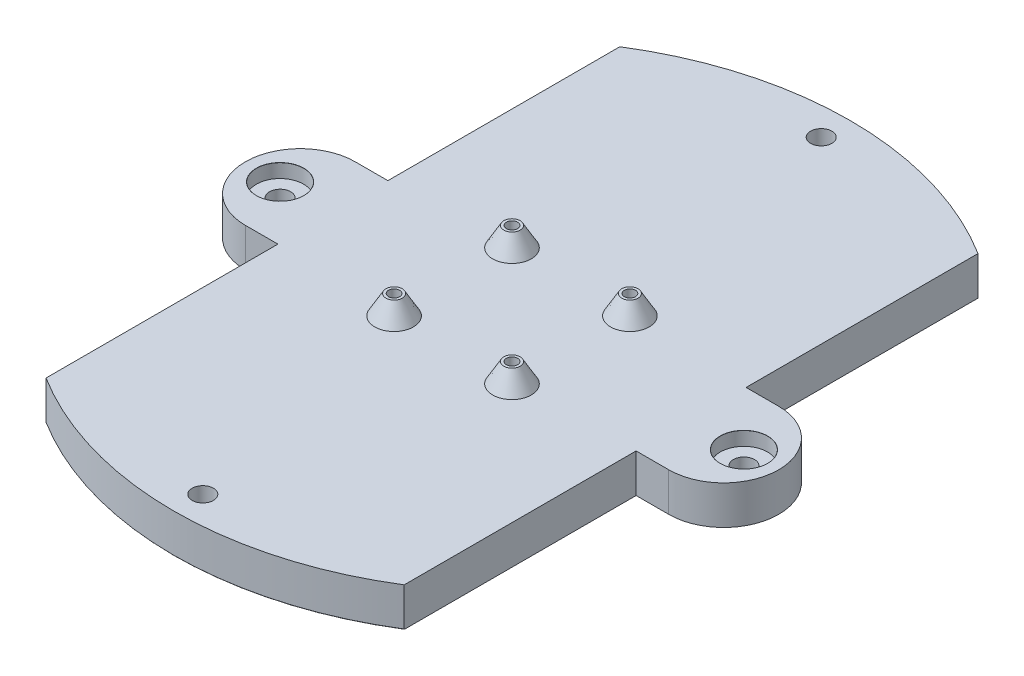
SolidWorks part; units mm, degrees
ref_plane "Front Plane" through (0, 0, 0) normal (0, 0, 1) x (1, 0, 0)
ref_plane "Top Plane" through (0, 0, 0) normal (0, 1, 0) x (1, 0, 0)
ref_plane "Right Plane" through (0, 0, 0) normal (1, 0, 0) x (0, 0, -1)
sketch "Sketch1" plane through (0, 0, 0) normal (0, 1, 0) x (1, 0, 0)
  circle A0 centre (0, 0) radius 87.5
  dimension "D1" = 175
extrude "Boss-Extrude1" add sketch "Sketch1" along normal blind 10
sketch "Sketch2" plane through (0, 10, 0) normal (0, 1, 0) x (1, 0, 0)
  circle A0 centre (0, -80) radius 7.5
  circle A1 centre (-80, 0) radius 7.5
  circle A2 centre (0, 80) radius 7.5
  circle A3 centre (80, 0) radius 7.5
  circle A4 centre (0, 0) radius 87.5 construction
  dimension "D1" = 15
extrude "Boss-Extrude2" add sketch "Sketch2" along normal blind 80
sketch "Sketch3" plane through (0, 0, 0) normal (0, -1, 0) x (-1, 0, 0)
  circle A0 centre (-80, 0) radius 7.5 construction
  circle A1 centre (0, 80) radius 7.5 construction
  circle A2 centre (80, 0) radius 7.5 construction
  circle A3 centre (0, -80) radius 7.5 construction
  point P0 (-80, 0)
  point P2 (0, 80)
  point P4 (80, 0)
  point P6 (0, -80)
hole_wizard "CBORE for M5 Hex Head Bolt1" positions "Sketch3" profile "Sketch4" counterbore size "M5" standard "ANSI Metric"
sketch "Sketch4" plane through (80, 0, 0) normal (1, 0, 0) x (0, 0, -1)
  line L0 (0, 0) -> (0, 21.6524)
  line L1 (0, 21.6524) -> (2.75, 20)
  line L2 (2.75, 20) -> (2.75, 3.58)
  line L3 (2.75, 3.58) -> (6.12, 3.58)
  line L5 (6.12, 3.58) -> (6.12, 0.025)
  line L6 (6.12, 0.025) -> (6.145, 0)
  line L7 (6.145, 0) -> (0, 0)
  line L8 (-6.12, 0.025) -> (-6.145, 0) construction
  line L10 (0, 21.6524) -> (-2.75, 20) construction
  line L11 (0, -6.35) -> (0, 107.95) construction
  dimension "Hole Dia." = 5.5
  dimension "Hole Depth" = 20
  dimension "C'Bore Dia." = 12.24
  dimension "C'Bore Depth" = 3.58
  dimension "Near C'Sink Dia." = 12.29
  dimension "Near C'Sink Angle" = 90
  dimension "Drill Angle" = 118
sketch "Sketch5" plane through (0, 10, 0) normal (0, 1, 0) x (1, 0, 0)
  circle A0 centre (0, 0) radius 87.5
  arc A1 (0, 87.5) -> (-87.5, 0) centre (0, 0) ccw construction
extrude "Cut-Extrude1" cut sketch "Sketch5" along normal blind 80
fillet "Fillet1" radius 0.1 1 edges at (0, 0, 87.5)
sketch "Sketch6" plane through (0, 10, 0) normal (0, 1, 0) x (1, 0, 0)
  line L5 (-15.25, 15.25) -> (15.25, 15.25) construction
  line L6 (-15.25, 15.25) -> (-15.25, -15.25) construction
  line L7 (-15.25, -15.25) -> (15.25, -15.25) construction
  line L8 (15.25, 15.25) -> (15.25, -15.25) construction
  line L9 (0, -15.25) -> (0, 15.25) construction
  line L10 (-15.25, 0) -> (15.25, 0) construction
  circle A2 centre (-15.25, 15.25) radius 5
  circle A3 centre (15.25, 15.25) radius 5
  circle A4 centre (15.25, -15.25) radius 5
  circle A5 centre (-15.25, -15.25) radius 5
  point P0 (0, 0)
  dimension "D3" = 10
  dimension "D1" = 30.5
  dimension "D2" = 30.5
extrude "Boss-Extrude3" add sketch "Sketch6" along normal blind 5 draft 30
sketch "Sketch7" plane through (0, 15, 0) normal (0, 1, 0) x (1, 0, 0)
  circle A0 centre (-15.25, 15.25) radius 1.45
  circle A1 centre (15.25, 15.25) radius 1.45
  circle A2 centre (15.25, -15.25) radius 1.45
  circle A3 centre (-15.25, -15.25) radius 1.45
  dimension "D1" = 2.9
extrude "Cut-Extrude2" cut sketch "Sketch7" against normal blind 8
sketch "Sketch10" plane through (0, 0, 0) normal (0, -1, 0) x (1, 0, 0)
  line L4 (0, -8.25) -> (0, 8.25) construction
  line L9 (-86.3361, -14.2241) -> (-46.3361, -14.2241)
  line L10 (-46.3361, -14.2241) -> (-46.3361, -74.2241)
  line L11 (-46.3361, 14.2241) -> (-46.3361, 74.2241)
  line L12 (-46.3361, 14.2241) -> (-86.3361, 14.2241)
  line L13 (46.3361, 14.2241) -> (86.3361, 14.2241)
  line L14 (46.3361, 14.2241) -> (46.3361, 74.2241)
  line L15 (46.3361, -14.2241) -> (46.3361, -74.2241)
  line L16 (86.3361, -14.2241) -> (46.3361, -14.2241)
  arc A0 (46.3361, 74.2241) -> (86.3361, 14.2241) centre (0, 0) cw
  circle A5 centre (0, 0) radius 87.5 construction
  arc A6 (-86.3361, -14.2241) -> (-46.3361, -74.2241) centre (0, 0) ccw
  arc A7 (-46.3361, 74.2241) -> (-86.3361, 14.2241) centre (0, 0) ccw
  arc A8 (86.3361, -14.2241) -> (46.3361, -74.2241) centre (0, 0) cw
  dimension "D1" = 60
  dimension "D2" = 40
  dimension "D3" = 60
extrude "Cut-Extrude5" cut sketch "Sketch10" against normal blind 10
sketch "Sketch12" plane through (0, 10, 0) normal (0, 1, 0) x (1, 0, 0)
  circle A0 centre (-80, 0) radius 2.75 construction
  circle A1 centre (80, 0) radius 2.75 construction
  point P0 (-60, 0)
  point P2 (60, 0)
  dimension "D1" = 20
  dimension "D2" = 20
hole_wizard "CBORE for M5 Hex Head Bolt2" positions "Sketch12" profile "Sketch13" counterbore size "M5" standard "ANSI Metric" end condition through all
sketch "Sketch13" plane through (-60, 10, 0) normal (1, 0, 0) x (0, 0, 1)
  line L0 (0, 0) -> (0, 10)
  line L1 (0, 10) -> (2.75, 10)
  line L3 (2.75, 10) -> (2.75, 3.58)
  line L4 (6.12, 3.58) -> (2.75, 3.58)
  line L5 (6.12, 3.58) -> (6.12, 0.025)
  line L6 (6.12, 0.025) -> (6.145, 0)
  line L7 (6.145, 0) -> (0, 0)
  line L8 (-6.12, 0.025) -> (-6.145, 0) construction
  line L11 (0, -6.35) -> (0, 107.95) construction
  dimension "Thru Hole Dia." = 5.5
  dimension "Thru Hole Depth" = 10
  dimension "C'Bore Dia." = 12.24
  dimension "C'Bore Depth" = 3.58
  dimension "Near C'Sink Dia." = 12.29
  dimension "Near C'Sink Angle" = 90
sketch "Sketch14" plane through (0, 10, 0) normal (0, 1, 0) x (1, 0, 0)
  line L1 (-69, 14.2241) -> (-69, -14.2241)
  line L3 (69, 14.2241) -> (69, -14.2241)
  line L6 (-46.3361, 14.2241) -> (-86.3361, 14.2241) construction
  line L7 (-86.3361, -14.2241) -> (-46.3361, -14.2241) construction
  line L8 (86.3361, 14.2241) -> (46.3361, 14.2241) construction
  line L9 (46.3361, -14.2241) -> (86.3361, -14.2241) construction
  line L11 (69, 14.2241) -> (99, 14.2241)
  line L12 (69, 14.2241) -> (69, -14.2241)
  line L13 (69, -14.2241) -> (99, -14.2241)
  line L14 (99, 14.2241) -> (99, -14.2241)
  line L15 (-69, 14.2241) -> (-99, 14.2241)
  line L16 (-69, 14.2241) -> (-69, -14.2241)
  line L17 (-69, -14.2241) -> (-99, -14.2241)
  line L18 (-99, 14.2241) -> (-99, -14.2241)
  circle A0 centre (60, 0) radius 2.75 construction
  circle A1 centre (-60, 0) radius 2.75 construction
  line M13 (-46.3361, 14.2241) -> (-86.3361, 14.2241)
  arc M14 (-86.3361, 14.2241) -> (-86.3361, -14.2241) centre (0, 0) ccw
  line M15 (-86.3361, -14.2241) -> (-46.3361, -14.2241)
  line M19 (46.3361, -14.2241) -> (86.3361, -14.2241)
  arc M20 (86.3361, -14.2241) -> (86.3361, 14.2241) centre (0, 0) ccw
  line M21 (86.3361, 14.2241) -> (46.3361, 14.2241)
  circle M30 centre (80, 0) radius 2.75
  circle M32 centre (-80, 0) radius 2.75
  dimension "D1" = 9
  dimension "D2" = 9
  dimension "D3" = 30
  dimension "D4" = 30
extrude "Cut-Extrude6" cut sketch "Sketch14" against normal blind 70 contours L1 M13 M14 M15 M32 | L3 M21 M19 M20 M30 region at (-69.3393, 10, 0) region at (77.6681, 10, -13.8847)
fillet "Fillet2" 2 edges at (-69, 5, -14.2241) (-69, 5, 14.2241) type full round first side face at (-57.6681, 5, -14.2241) second side face at (-57.6681, 5, 14.2241) middle face at (-69, 5, 0)
fillet "Fillet3" 2 edges at (69, 5, -14.2241) (69, 5, 14.2241) type full round first side face at (57.6681, 5, -14.2241) second side face at (57.6681, 5, 14.2241) middle face at (69, 5, 0)
